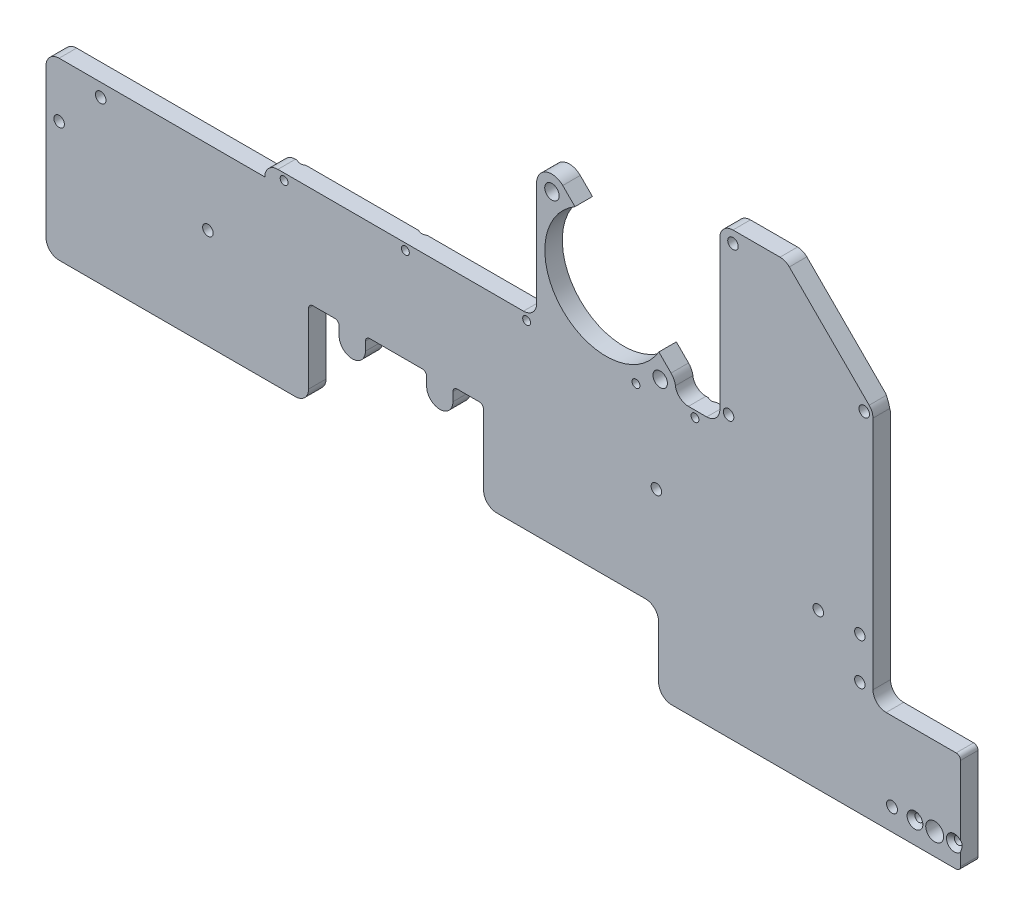
SolidWorks part; units mm, degrees
material "3.1355 (EN-AW 2024)"
ref_plane "Спереди" through (0, 0, 0) normal (0, 0, 1) x (1, 0, 0)
ref_plane "Сверху" through (0, 0, 0) normal (0, 1, 0) x (1, 0, 0)
ref_plane "Справа" through (0, 0, 0) normal (1, 0, 0) x (0, 0, -1)
sketch "Model" plane through (0, 0, 0) normal (0, 0, 1) x (1, 0, 0)
  line L1 (122.3431, 31.8431) -> (128, 37.5) construction
  line L3 (112.1256, 49.8744) -> (112.1256, 23)
  line L11 (154, 23) -> (154, 0)
  line L19 (0, 0) -> (0, 20)
  line L39 (0, 20) -> (50, 20)
  line L44 (112.1256, 23) -> (50, 23)
  line L49 (50, 23) -> (50, 20)
  line L54 (0, 0) -> (0, -20)
  line L55 (0, -20) -> (60, -20)
  line L56 (60, -20) -> (60, 0)
  line L57 (60, 0) -> (154, 0)
  line L60 (143.8744, 25.1256) -> (143.8744, 23)
  line L62 (143.8744, 23) -> (154, 23)
  line L65 (142.8492, 27.6005) -> (140.06, 30.3897)
  line L69 (120.8897, 49.56) -> (118.1005, 52.3492)
  line L71 (128, 37.5) -> (140.3744, 25.1256) construction
  line L72 (128, 37.5) -> (115.6256, 49.8744) construction
  circle A10 centre (140.3744, 25.1256) radius 1
  circle A12 centre (115.6256, 49.8744) radius 1
  arc A14 (143.8744, 25.1256) -> (142.8492, 27.6005) centre (140.3744, 25.1256) ccw
  arc A44 (118.1005, 52.3492) -> (112.1256, 49.8744) centre (115.6256, 49.8744) ccw
  arc A46 (120.8897, 49.56) -> (140.06, 30.3897) centre (128, 37.5) ccw
  circle A47 centre (122.3431, 31.8431) radius 2.5 construction
  dimension "D3" = 5
  dimension "D8" = 128
  dimension "D11" = 37.5
  dimension "D15" = 20
  dimension "D26" = 2
  dimension "D27" = 3.5
  dimension "D4" = 28
  dimension "D12" = 45
  dimension "D5" = 20
  dimension "D6" = 8
  dimension "D7" = 50
  dimension "D10" = 35
  dimension "D13" = 23
  dimension "D18" = 154
  dimension "D22" = 60
extrude "База" add sketch "Model" against normal blind 4
sketch "Эскиз15" plane through (0, 0, -4) normal (0, 0, 1) x (1, 0, 0)
  line L0 (60, 0) -> (154, 0) construction
  line L1 (67, 0) -> (73, 0)
  line L2 (67, 0) -> (67, -6)
  line L3 (67, -6) -> (73, -6)
  line L4 (73, 0) -> (73, -6)
  line L5 (60, -20) -> (60, 0) construction
  line L6 (87, 0) -> (93, 0)
  line L7 (87, 0) -> (87, -6)
  line L8 (87, -6) -> (93, -6)
  line L9 (93, 0) -> (93, -6)
  point P10 (70, -6)
  point P12 (90, -6)
  dimension "D1" = 6
  dimension "D2" = 10
  dimension "D3" = 20
extrude "Вставка в профиль 20*40" add sketch "Эскиз15" along normal up to surface (4 mm away) up to face at (116.6256, 49.8744, 0)
hole_wizard "Крепление двигателя M4" positions "Эскиз3" profile "Эскиз4" tap size "M4" standard "DIN" end condition through all
sketch "Эскиз3" plane through (0, 0, 0) normal (0, 0, 1) x (1, 0, 0)
  point P0 (115.6256, 49.8744)
  point P3 (140.3744, 25.1256)
sketch "Эскиз4" plane through (115.6256, 49.8744, 0) normal (1, 0, 0) x (0, -1, 0)
  line L0 (0, 0) -> (0, 4)
  line L1 (0, 4) -> (1.65, 4)
  line L2 (1.65, 4) -> (1.65, 0)
  line L5 (1.65, 0) -> (0, 0)
  line L11 (0, -6.35) -> (0, 107.95) construction
  dimension "Диаметр проходного сверла" = 3.3
  dimension "Глубина проходного сверла" = 4
cosmetic thread "Отверстие резьбы1" parameters "D2"=4
cosmetic thread "Отверстие резьбы2" parameters "D2"=4
sketch "Эскиз7" plane through (0, 0, -4) normal (0, 0, 1) x (1, 0, 0)
  line L0 (154, 23) -> (154, 63)
  line L1 (154, 63) -> (169, 63)
  line L2 (169, 63) -> (189, 43)
  line L3 (189, 43) -> (189, -20)
  line L5 (100, -20) -> (100, 0)
  line L6 (60, 0) -> (67, 0) construction
  line L7 (60, -20) -> (60, 0) construction
  line L8 (154, 0) -> (154, 23) construction
  line L9 (100, 0) -> (154, 0)
  line L10 (154, 0) -> (154, 23)
  line L11 (189, -20) -> (100, -20)
  dimension "D1" = 40
  dimension "D2" = 15
  dimension "D3" = 135
  dimension "D4" = 20
  dimension "D5" = 35
  dimension "D8" = 40
extrude "Панель управления" add sketch "Эскиз7" along normal up to surface (4 mm away) up to face at (117.2756, 49.8744, 0)
fillet "Скругление5" radius 1 6 edges at (93, 0, -2) (87, 0, -2) (73, 0, -2) (67, 0, -2) (100, 0, -2) (60, 0, -2)
hole_wizard "Крепление M2" positions "Эскиз10" profile "Эскиз11" countersink size "M2" standard "DIN" end condition through all
sketch "Эскиз10" plane through (0, 0, -4) normal (0, 0, -1) x (-1, 0, 0)
  point P0 (-3, 7.5)
  point P3 (-12.5, 17)
  point P30 (-186, -2.5)
  point P33 (-186, -12)
  point P36 (-176.5, -2.5)
  point P64 (-156, 25.95)
  point P67 (-157, 60.32)
  point P68 (-187, 42.08)
  dimension "D1" = 3
  dimension "D2" = 12.5
  dimension "D3" = 7.5
  dimension "D4" = 17
sketch "Эскиз11" plane through (3, 7.5, -4) normal (1, 0, 0) x (0, 1, 0)
  line L0 (0, 0) -> (0, 4)
  line L1 (0, 4) -> (1.2, 4)
  line L2 (1.2, 4) -> (1.2, 1)
  line L3 (1.2, 1) -> (2.2, 0)
  line L5 (2.2, 0) -> (0, 0)
  line L6 (-1.2, 1) -> (-2.2, 0) construction
  line L11 (0, -6.35) -> (0, 107.95) construction
  dimension "Диаметр сквозного отверстия" = 2.4
  dimension "Глубина сквозного отверстия" = 4
  dimension "Диаметр передней зенковки" = 4.4
  dimension "Угол передней зенковки" = 90
hole_wizard "Зенковка для винта M1.6" positions "Эскиз16" profile "Эскиз17" countersink size "M1.6" standard "DIN" end condition through all
sketch "Эскиз16" plane through (0, 0, -4) normal (0, 0, -1) x (-1, 0, 0)
  line L0 (-50, 20) -> (0, 20) construction
  point P0 (-148.32, 21.5)
  point P3 (-134.84, 21.5)
  point P6 (-109.84, 21.5)
  point P9 (-82.13, 21.5)
  point P12 (-54.42, 21.5)
  dimension "D1" = 1.5
  dimension "D2" = 54.42
  dimension "D3" = 27.71
  dimension "D4" = 27.71
  dimension "D5" = 25
  dimension "D6" = 13.48
sketch "Эскиз17" plane through (148.32, 21.5, -4) normal (1, 0, 0) x (0, 1, 0)
  line L0 (0, 0) -> (0, 4)
  line L1 (0, 4) -> (0.9, 4)
  line L2 (0.9, 4) -> (0.9, 0.9)
  line L3 (0.9, 0.9) -> (1.8, 0)
  line L5 (1.8, 0) -> (0, 0)
  line L6 (-0.9, 0.9) -> (-1.8, 0) construction
  line L11 (0, -6.35) -> (0, 107.95) construction
  dimension "Диаметр сквозного отверстия" = 1.8
  dimension "Глубина сквозного отверстия" = 4
  dimension "Диаметр передней зенковки" = 3.6
  dimension "Угол передней зенковки" = 90
sketch "Эскиз18" plane through (0, 0, -4) normal (0, 0, -1) x (-1, 0, 0)
  line L1 (-140, -15) -> (-209, -15)
  line L2 (-140, -15) -> (-140, -38)
  line L3 (-140, -38) -> (-209, -38)
  line L4 (-209, -15) -> (-209, -38)
  line L5 (-189, -20) -> (-189, 43) construction
  line L6 (-100, -20) -> (-189, -20) construction
  line L7 (-100, -1) -> (-100, -20) construction
  dimension "D1" = 23
  dimension "D2" = 20
  dimension "D3" = 40
  dimension "D4" = 5
extrude "Бобышка-Вытянуть1" add sketch "Эскиз18" against normal up to surface (4 mm away) up to face at (147.42, 21.5, 0)
fillet "Скругление4" radius 3 14 edges at (0, 20, -2) (112.1256, 23, -2) (50, 23, -2) (143.8744, 23, -2) (154, 23, -2) (154, 63, -2) (189, 43, -2) (169, 63, -2) (140, -20, -2) (140, -38, -2) (60, -20, -2) (189, -15, -2) (0, -20, -2) (100, -20, -2)
sketch "Эскиз19" plane through (0, 0, -4) normal (0, 0, -1) x (-1, 0, 0)
  circle A0 centre (-203.1, -33) radius 2.05
  dimension "D1" = 4.1
  dimension "D2" = 33
  dimension "D3" = 203.1
extrude "Вырез-Вытянуть1" cut sketch "Эскиз19" against normal up to surface (4 mm away) up to face at (108.4236, 8.2735, 0)
hole_wizard "Зенковка для винта с полупотайной головкой M1.61" positions "Эскиз20" profile "Эскиз21" countersink size "M1.6" standard "ISO" end condition through all
sketch "Эскиз20" plane through (0, 0, 0) normal (0, 0, 1) x (1, 0, 0)
  line L0 (207.6, -33) -> (203.1, -33) construction
  line L1 (203.1, -33) -> (198.6, -33) construction
  point P0 (207.6, -33)
  point P2 (198.6, -33)
  dimension "D1" = 9
sketch "Эскиз21" plane through (207.6, -33, 0) normal (1, 0, 0) x (0, -1, 0)
  line L0 (0, 0) -> (0, 4.1238)
  line L1 (0, 4.1238) -> (0.9, 4.1238)
  line L2 (0.9, 4.1238) -> (0.9, 0.9)
  line L3 (0.9, 0.9) -> (1.8, 0)
  line L5 (1.8, 0) -> (0, 0)
  line L6 (-0.9, 0.9) -> (-1.8, 0) construction
  line L11 (0, -6.35) -> (0, 107.95) construction
  dimension "Диаметр сквозного отверстия" = 1.8
  dimension "Глубина сквозного отверстия" = 4.1238
  dimension "Диаметр передней зенковки" = 3.6
  dimension "Угол передней зенковки" = 90
hole_wizard "Отверстие обработанное метчиком M31" positions "Эскиз22" profile "Эскиз23" tap size "M3" standard "DIN" end condition through all
sketch "Эскиз22" plane through (0, 0, 0) normal (0, 0, 1) x (1, 0, 0)
  circle A0 centre (203.1, -33) radius 2.05 construction
  point P0 (193.35, -33)
  dimension "D1" = 9.75
  dimension "D2" = 33
sketch "Эскиз23" plane through (193.35, -33, 0) normal (1, 0, 0) x (0, -1, 0)
  line L0 (0, 0) -> (0, 4.1238)
  line L1 (0, 4.1238) -> (1.25, 4.1238)
  line L2 (1.25, 4.1238) -> (1.25, 0)
  line L5 (1.25, 0) -> (0, 0)
  line L11 (0, -6.35) -> (0, 107.95) construction
  dimension "Диаметр проходного сверла" = 2.5
  dimension "Глубина проходного сверла" = 4.1238
cosmetic thread "Отверстие резьбы3" parameters "D2"=3
fillet "Скругление6" radius 1 2 edges at (209, -38, -2) (209, -15, -2)
fillet "Скругление7" 2 edges at (67, -6, -2) (73, -6, -2) type full round first side face at (67, -3.5, -2) second side face at (73, -3.5, -2) middle face at (70, -6, -2)
fillet "Скругление8" 2 edges at (93, -6, -2) (87, -6, -2) type full round first side face at (93, -3.5, -2) second side face at (87, -3.5, -2) middle face at (90, -6, -2)
hole_wizard "УровеньПрижима-M2" positions "Эскиз24" profile "Эскиз25" countersink size "M2" standard "DIN" end condition through all
sketch "Эскиз24" plane through (0, 0, -4) normal (0, 0, -1) x (-1, 0, 0)
  point P3 (-139.5, 2.95)
  point P9 (-37, 2.95)
  dimension "D2" = 102.5
  dimension "D3" = 37
  dimension "D4" = 2.95
sketch "Эскиз25" plane through (139.5, 2.95, -4) normal (1, 0, 0) x (0, 1, 0)
  line L0 (0, 0) -> (0, 4)
  line L1 (0, 4) -> (1.2, 4)
  line L2 (1.2, 4) -> (1.2, 1)
  line L3 (1.2, 1) -> (2.2, 0)
  line L5 (2.2, 0) -> (0, 0)
  line L6 (-1.2, 1) -> (-2.2, 0) construction
  line L11 (0, -6.35) -> (0, 107.95) construction
  dimension "Диаметр сквозного отверстия" = 2.4
  dimension "Глубина сквозного отверстия" = 4
  dimension "Диаметр передней зенковки" = 4.4
  dimension "Угол передней зенковки" = 90
